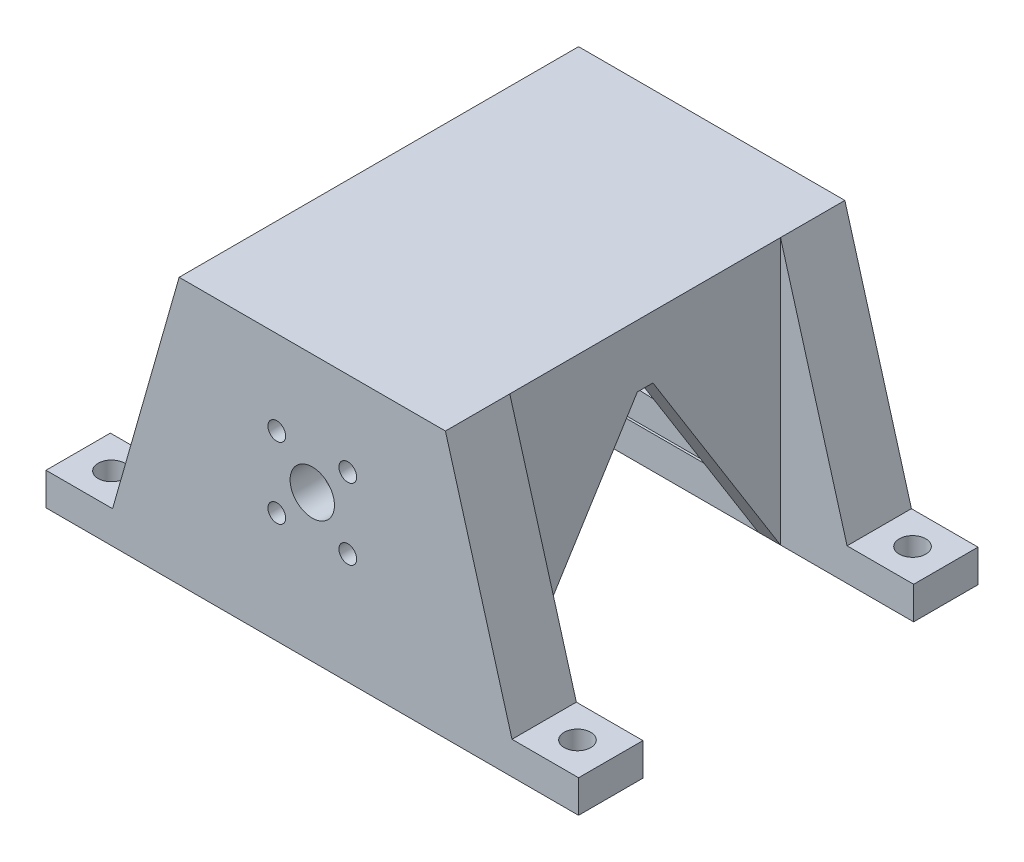
SolidWorks part; units mm, degrees
ref_plane "Front Plane" through (0, 0, 0) normal (0, 0, 1) x (1, 0, 0)
ref_plane "Top Plane" through (0, 0, 0) normal (0, 1, 0) x (1, 0, 0)
ref_plane "Right Plane" through (0, 0, 0) normal (1, 0, 0) x (0, 0, -1)
sketch "Sketch1" plane through (0, 0, 0) normal (0, 0, 1) x (1, 0, 0)
  line L2 (-30, -30) -> (-30, 30)
  line L3 (-30, 30) -> (30, 30)
  line L4 (30, -30) -> (30, 30)
  line L5 (-30, -30) -> (30, 30) construction
  line L6 (-30, 30) -> (30, -30) construction
  line L11 (30, -30) -> (-30, -30)
  point P0 (0, 0)
  dimension "D1" = 60
extrude "Boss-Extrude1" add sketch "Sketch1" along normal blind 90
sketch "Sketch5" plane through (0, 0, 0) normal (0, 0, -1) x (-1, 0, 0)
  line L0 (-8, -5) -> (8, -5) construction
  line L1 (-8, -5) -> (-8, 11) construction
  line L2 (-8, 11) -> (8, 11) construction
  line L3 (8, -5) -> (8, 11) construction
  line L4 (-8, -5) -> (8, 11) construction
  line L5 (-8, 11) -> (8, -5) construction
  circle A0 centre (-8, 11) radius 2
  circle A1 centre (8, 11) radius 2
  circle A2 centre (8, -5) radius 2
  circle A3 centre (-8, -5) radius 2
  circle A4 centre (0, 3) radius 5
  point P0 (0, 3)
  dimension "D2" = 4
  dimension "D3" = 10
  dimension "D1" = 16
  dimension "D4" = 3
extrude "Cut-Extrude4" cut sketch "Sketch5" against normal through all and the other way through all
sketch "Sketch6" [suppressed] plane through (0, 0, 0) normal (0, 0, -1) x (-1, 0, 0)
  circle A0 centre (0, 3) radius 19.25
  dimension "D2" = 38.5
  dimension "D1" = 3
extrude "Cut-Extrude5" [suppressed] cut sketch "Sketch6" against normal through all
sketch "Sketch7" plane through (-30, 0, 0) normal (-1, 0, 0) x (0, 0, 1)
  line L1 (14, 16) -> (76, 16)
  line L2 (14, 16) -> (14, -34)
  line L3 (14, -34) -> (76, -34)
  line L4 (76, 16) -> (76, -34)
  line L5 (0, 30) -> (0, -30) construction
  line L7 (90, 30) -> (0, 30) construction
  dimension "D1" = 62
  dimension "D2" = 14
  dimension "D3" = 14
  dimension "D4" = 50
extrude "Cut-Extrude6" cut sketch "Sketch7" against normal through all both and the other way through all
sketch "Sketch8" plane through (0, 0, 0) normal (0, 0, -1) x (-1, 0, 0)
  circle A0 centre (0, 3) radius 19.3
  dimension "D1" = 38.6
extrude "Cut-Extrude7" cut sketch "Sketch8" against normal blind 83
sketch "Sketch10" plane through (0, 16, 0) normal (0, -1, 0) x (1, 0, 0)
  line L0 (-30, 14) -> (-30, 76) construction
  line L1 (-30, 76) -> (-25, 76)
  line L2 (-30, 76) -> (-30, 45.5)
  line L3 (-30, 45.5) -> (-25, 45.5)
  line L4 (-25, 76) -> (-25, 45.5)
  line L5 (-30, 14) -> (-25, 14)
  line L6 (-30, 14) -> (-30, 44.5)
  line L7 (-30, 44.5) -> (-25, 44.5)
  line L8 (-25, 14) -> (-25, 44.5)
  line L9 (30, 76) -> (25, 76)
  line L10 (30, 76) -> (30, 45.5)
  line L11 (30, 45.5) -> (25, 45.5)
  line L12 (25, 76) -> (25, 45.5)
  line L13 (30, 14) -> (25, 14)
  line L14 (30, 14) -> (30, 44.5)
  line L15 (30, 44.5) -> (25, 44.5)
  line L16 (25, 14) -> (25, 44.5)
  line L17 (30, 76) -> (30, 14) construction
  line L18 (-14.265, 14) -> (-30, 14) construction
  line L19 (-30, 76) -> (30, 76) construction
  line L20 (30, 14) -> (-30, 14) construction
  dimension "D1" = 5
  dimension "D2" = 30.5
extrude "Boss-Extrude2" add sketch "Sketch10" along normal blind 46
chamfer "Chamfer1" distance 30 angle 58 6 edges at (27.5, -30, 44.5) (27.5, -30, 45.5) (-27.5, 16, 44.5) (-27.5, -30, 44.5) (-27.5, 16, 45.5) (-27.5, -30, 45.5)
sketch "Sketch11" plane through (-30, 0, 0) normal (-1, 0, 0) x (0, 0, 1)
  line L1 (0, 30) -> (14.5, 30)
  line L2 (0, 30) -> (0, -30)
  line L3 (0, -30) -> (14.5, -30)
  line L4 (14.5, 30) -> (14.5, -30)
  line L5 (75.5, -30) -> (90, -30)
  line L6 (75.5, -30) -> (75.5, 30)
  line L7 (75.5, 30) -> (90, 30)
  line L8 (90, -30) -> (90, 30)
extrude "Boss-Extrude3" add sketch "Sketch11" along normal blind 15
sketch "Sketch12" plane through (30, 0, 0) normal (1, 0, 0) x (0, 0, -1)
  line L1 (-90, 30) -> (-75.5, 30)
  line L2 (-90, 30) -> (-90, -30)
  line L3 (-90, -30) -> (-75.5, -30)
  line L4 (-75.5, 30) -> (-75.5, -30)
  line L5 (-14.5, -30) -> (0, -30)
  line L6 (-14.5, -30) -> (-14.5, 30)
  line L7 (-14.5, 30) -> (0, 30)
  line L8 (0, -30) -> (0, 30)
extrude "Boss-Extrude4" add sketch "Sketch12" along normal blind 15
chamfer "Chamfer2" distance 15 angle 74.1 4 edges at (-45, 30, 7.25) (-45, 30, 82.75) (45, 30, 82.75) (45, 30, 7.25)
sketch "Sketch13" plane through (45, 0, 0) normal (1, 0, 0) x (0, 0, -1)
  line L1 (-90, -22.6579) -> (-75.5, -22.6579)
  line L2 (-90, -22.6579) -> (-90, -30)
  line L3 (-90, -30) -> (-75.5, -30)
  line L4 (-75.5, -22.6579) -> (-75.5, -30)
  line L5 (-14.5, -22.6579) -> (0, -22.6579)
  line L6 (-14.5, -22.6579) -> (-14.5, -30)
  line L7 (-14.5, -30) -> (0, -30)
  line L8 (0, -22.6579) -> (0, -30)
extrude "Boss-Extrude5" add sketch "Sketch13" along normal blind 15 and the other way blind 105
hole_wizard "Ø6.0mm Dowel Hole1" positions "3DSketch1" profile "Sketch14" hole size "Ø6.0" standard "AS" end condition through all
sketch3d "3DSketch1"
  line L0 (45, -22.6579, 75.5) -> (60, -22.6579, 75.5) construction
  line L1 (60, -22.6579, 75.5) -> (60, -22.6579, 90) construction
  line L2 (45, -22.6579, 0) -> (60, -22.6579, 0) construction
  line L3 (60, -22.6579, 0) -> (60, -22.6579, 14.5) construction
  line L4 (-60, -22.6579, 0) -> (-60, -22.6579, 14.5) construction
  line L5 (-60, -22.6579, 14.5) -> (-45, -22.6579, 14.5) construction
  line L6 (-60, -22.6579, 90) -> (-45, -22.6579, 90) construction
  line L7 (-60, -22.6579, 75.5) -> (-60, -22.6579, 90) construction
  point P0 (52.5, -22.6579, 82.75)
  point P2 (52.5, -22.6579, 7.25)
  point P4 (-52.5, -22.6579, 7.25)
  point P6 (-52.5, -22.6579, 82.75)
  dimension "D1" = 7.25
  dimension "D2" = 7.5
  dimension "D3" = 7.25
  dimension "D4" = 7.5
  dimension "D5" = 7.5
  dimension "D6" = 7.25
  dimension "D7" = 7.25
  dimension "D8" = 7.5
sketch "Sketch14" plane through (52.5, -22.6579, 82.75) normal (1, 0, 0) x (0, 0, 1)
  line L0 (0, 0) -> (0, 7.3421)
  line L1 (0, 7.3421) -> (3, 7.3421)
  line L2 (3, 7.3421) -> (3, 0)
  line L5 (3, 0) -> (0, 0)
  line L11 (0, -6.35) -> (0, 107.95) construction
  dimension "Thru Hole Dia." = 6
  dimension "Thru Hole Depth" = 7.3421
